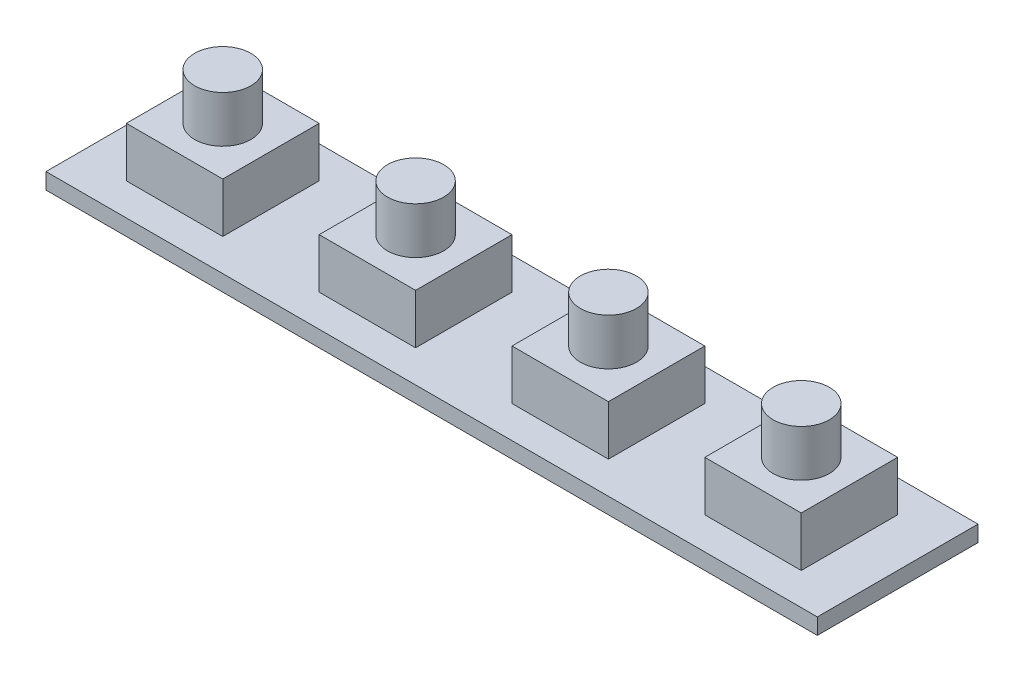
SolidWorks part; units mm, degrees
ref_plane "Front Plane" through (0, 0, 0) normal (0, 0, 1) x (1, 0, 0)
ref_plane "Top Plane" through (0, 0, 0) normal (0, 1, 0) x (1, 0, 0)
ref_plane "Right Plane" through (0, 0, 0) normal (1, 0, 0) x (0, 0, -1)
sketch "Sketch1" plane through (0, 0, 0) normal (0, 1, 0) x (1, 0, 0)
  line L1 (-24, 5) -> (24, 5)
  line L2 (-24, 5) -> (-24, -5)
  line L3 (-24, -5) -> (24, -5)
  line L4 (24, 5) -> (24, -5)
  line L5 (-24, 5) -> (24, -5) construction
  line L6 (-24, -5) -> (24, 5) construction
  point P0 (0, 0)
  dimension "D1" = 48
  dimension "D2" = 10
extrude "Boss-Extrude1" add sketch "Sketch1" along normal blind 1
sketch "Sketch2" plane through (0, 1, 0) normal (0, 1, 0) x (1, 0, 0)
  line L0 (-9, 3) -> (-3, 3)
  line L1 (-21, 3) -> (-15, 3)
  line L2 (-21, 3) -> (-21, -3)
  line L3 (-21, -3) -> (-15, -3)
  line L4 (-15, 3) -> (-15, -3)
  line L5 (-21, 3) -> (-15, -3) construction
  line L6 (-21, -3) -> (-15, 3) construction
  line L7 (-9, 3) -> (-9, -3)
  line L8 (-9, -3) -> (-3, -3)
  line L9 (-3, 3) -> (-3, -3)
  line L10 (-9, 3) -> (-3, -3) construction
  line L11 (-9, -3) -> (-3, 3) construction
  line L12 (3, 3) -> (9, 3)
  line L13 (3, 3) -> (3, -3)
  line L14 (3, -3) -> (9, -3)
  line L15 (9, 3) -> (9, -3)
  line L16 (3, 3) -> (9, -3) construction
  line L17 (3, -3) -> (9, 3) construction
  line L18 (15, 3) -> (21, 3)
  line L19 (15, 3) -> (15, -3)
  line L20 (15, -3) -> (21, -3)
  line L21 (21, 3) -> (21, -3)
  line L22 (15, 3) -> (21, -3) construction
  line L23 (15, -3) -> (21, 3) construction
  line L24 (24, -5) -> (24, 5) construction
  line L25 (24, 5) -> (-24, 5) construction
  point P0 (-18, 0)
  point P5 (-17.7505, -0.2195)
  point P6 (-17.6062, 0)
  point P7 (0, 0)
  point P8 (-6, 0)
  point P13 (6, 0)
  point P18 (18, 0)
  point P22 (-5.9267, 0)
  point P23 (5.4764, 0)
  point P24 (16.2948, 0)
  point P26 (-17.6065, 0)
  point P27 (-6, 0.0996)
  point P29 (6, 0.0996)
  point P31 (18, 0.0996)
  point P33 (-6, 0)
  point P34 (-5.4366, 0.0996)
  dimension "D1" = 6
  dimension "D2" = 6
  dimension "D3" = 6
  dimension "D4" = 6
  dimension "D5" = 6
  dimension "D6" = 6
  dimension "D7" = 6
  dimension "D8" = 6
  dimension "D9" = 12
  dimension "D10" = 12
  dimension "D11" = 12
  dimension "D12" = 6
  dimension "D13" = 5
  dimension "D14" = 5
  dimension "D15" = 5
  dimension "D16" = 5
extrude "Boss-Extrude2" add sketch "Sketch2" along normal blind 3
extrude "Boss-Extrude3" add sketch "Sketch2<2>" along normal blind 3.1
sketch "Sketch2<2>" plane through (0, 1, 0) normal (0, 1, 0) x (1, 0, 0) same geometry as "Sketch2"
sketch "Sketch4" plane through (0, 4.1, 0) normal (0, 1, 0) x (1, 0, 0)
  line L0 (15, 3) -> (15, -3) construction
  line L1 (15, -3) -> (21, -3) construction
  line L2 (3, 3) -> (3, -3) construction
  line L3 (3, -3) -> (9, -3) construction
  line L4 (-9, 3) -> (-9, -3) construction
  line L5 (-9, -3) -> (-3, -3) construction
  line L6 (-21, 3) -> (-21, -3) construction
  line L7 (-21, -3) -> (-15, -3) construction
  circle A0 centre (-18, 0) radius 1.75
  circle A1 centre (-6, 0) radius 1.75
  circle A2 centre (6, 0) radius 1.75
  circle A3 centre (18, 0) radius 1.75
  point P24 (0, 0)
  dimension "D1" = 3.5
  dimension "D2" = 3.5
  dimension "D3" = 3.5
  dimension "D4" = 3.5
  dimension "D5" = 3
  dimension "D6" = 3
  dimension "D7" = 3
  dimension "D8" = 3
  dimension "D9" = 3
  dimension "D10" = 3
  dimension "D11" = 3
  dimension "D12" = 3
extrude "Boss-Extrude4" add sketch "Sketch4" along normal blind 2.9 contours A0 | A3 | A2 | A1 region at (-18, 4.1, 0) region at (-6, 4.1, 0) region at (6, 4.1, 0) region at (18, 4.1, 0)
